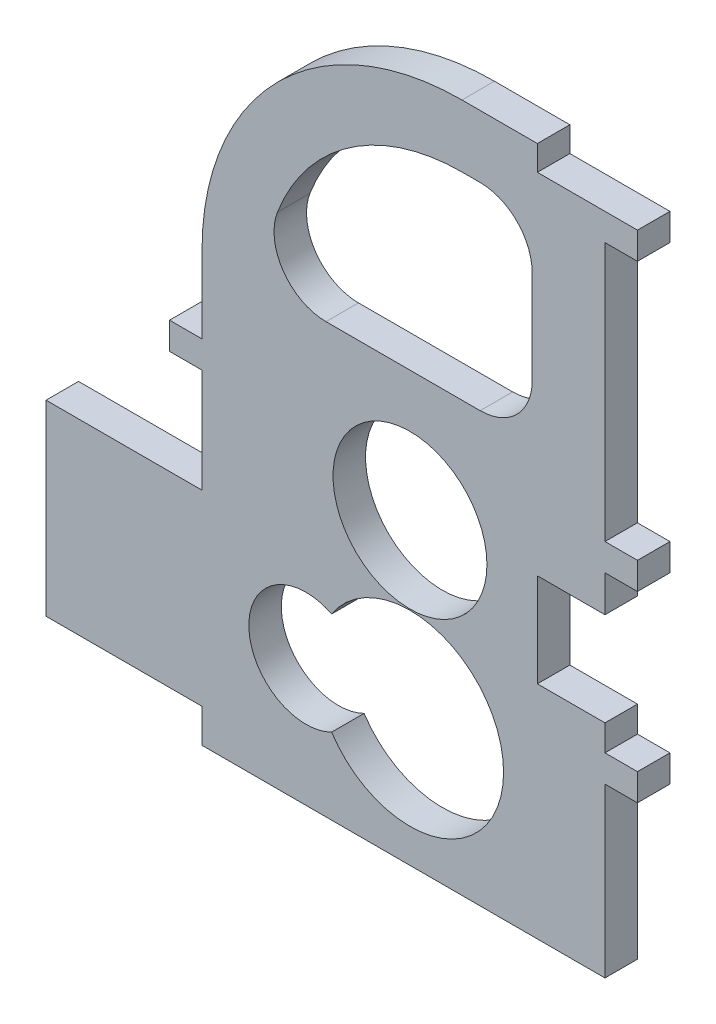
SolidWorks part; units mm, degrees
material "Balsa"
ref_plane "Front Plane" through (0, 0, 0) normal (0, 0, 1) x (1, 0, 0)
ref_plane "Top Plane" through (0, 0, 0) normal (0, 1, 0) x (1, 0, 0)
ref_plane "Right Plane" through (0, 0, 0) normal (1, 0, 0) x (0, 0, -1)
sketch "Sketch1" plane through (0, 0, 0) normal (0, 0, 1) x (1, 0, 0)
  line L0 (0, -1000) -> (0, 49000) construction
  line L1 (-1000, 0) -> (49000, 0) construction
  line L2 (0, -8.382) -> (-5.08, -8.382)
  line L3 (9.525, 16.51) -> (11.1125, 16.51)
  line L4 (2.54, 19.05) -> (9.525, 19.05)
  line L5 (9.525, -14.605) -> (-10.16, -14.605)
  line L6 (-10.16, -14.605) -> (-10.16, 6.35)
  line L7 (9.525, 19.05) -> (9.525, -14.605)
  line L8 (-11.7475, 1.27) -> (-10.16, 1.27)
  line L9 (-11.7475, 1.27) -> (-11.7475, 2.5908)
  line L10 (-11.7475, 2.5908) -> (-10.16, 2.5908)
  line L11 (-10.16, 1.27) -> (-10.16, 2.5908)
  line L12 (9.525, 2.54) -> (11.1125, 2.54)
  line L13 (9.525, 2.54) -> (9.525, 3.8608)
  line L14 (9.525, 3.8608) -> (11.1125, 3.8608)
  line L15 (11.1125, 2.54) -> (11.1125, 3.8608)
  line L16 (9.525, 16.51) -> (9.525, 17.8308)
  line L17 (9.525, 17.8308) -> (11.1125, 17.8308)
  line L18 (11.1125, 16.51) -> (11.1125, 17.8308)
  line L19 (-7.112, 6.35) -> (5.969, 6.35)
  line L20 (-10.16, -12.954) -> (-17.78, -12.954)
  line L21 (5.969, 6.35) -> (5.969, 16.002)
  line L22 (-10.16, -3.81) -> (-17.78, -3.81)
  line L23 (-17.78, -12.954) -> (-17.78, -3.81)
  line L24 (5.969, 16.002) -> (2.54, 16.002)
  line L27 (9.525, -6.4008) -> (11.1125, -6.4008)
  line L28 (9.525, -6.4008) -> (9.525, -5.08)
  line L29 (9.525, -5.08) -> (11.1125, -5.08)
  line L30 (11.1125, -6.4008) -> (11.1125, -5.08)
  circle A0 centre (0, 0) radius 3.7592
  arc A1 (-3.829, -10.8803) -> (-3.829, -5.8837) centre (0, -8.382) ccw
  arc A2 (-3.829, -5.8837) -> (-3.829, -10.8803) centre (-5.08, -8.382) ccw
  arc A3 (2.54, 19.05) -> (-10.16, 6.35) centre (2.54, 6.35) ccw
  arc A4 (2.54, 16.002) -> (-7.112, 6.35) centre (2.54, 6.35) ccw
  arc A5 (2.54, 19.05) -> (-10.16, 6.35) centre (2.54, 6.35) ccw construction
  dimension "D1" = 7.5184
  dimension "D4" = 9.144
  dimension "D3" = 19.685
  dimension "D5" = 8.382
  dimension "D9" = 12.7
  dimension "D10" = 1.5875
  dimension "D16" = 3.81
  dimension "D7" = 5.588
  dimension "D6" = 5.08
  dimension "D8" = 9.525
  dimension "D11" = 9.144
  dimension "D12" = 1.3208
  dimension "D13" = 1.3208
  dimension "D14" = 1.5875
  dimension "D15" = 2
  dimension "D17" = 14.605
  dimension "D18" = 19.05
  dimension "D19" = 16.51
  dimension "D20" = 3.048
  dimension "D21" = 3.556
  dimension "D22" = 1.3208
  dimension "D23" = 1.5875
  dimension "D24" = 5.08
  dimension "D25" = 1.27
  dimension "D26" = 7.62
  dimension "D27" = 2.54
extrude "Boss-Extrude1" add sketch "Sketch1" along normal blind 1.5875 contours L4 A3 L7 A0 | L10 L9 L8 | L3 L18 L17 L7 | L12 L15 L14 L7 | A3 | L27 L30 L29 L7 | L23 L20 L6 L22 region at (10.3187, 17.1704, 0) region at (9.1351, 10.1854, 0) region at (10.3187, 3.2004, 0) region at (10.3187, -5.7404, 0) region at (-10.9538, 1.9304, 0) region at (-13.97, -8.382, 0)
sketch "Sketch2" plane through (0, 0, 1.5875) normal (0, 0, 1) x (1, 0, 0)
  line L1 (6.223, -3.81) -> (9.525, -3.81)
  line L2 (6.223, -3.81) -> (6.223, 0.762)
  line L3 (6.223, 0.762) -> (9.525, 0.762)
  line L4 (9.525, -3.81) -> (9.525, 0.762)
  line L5 (9.525, 2.54) -> (9.525, -5.08) construction
  line L7 (9.525, 19.05) -> (9.525, 17.8308) construction
  line L9 (6.223, 17.8308) -> (9.525, 17.8308)
  line L10 (6.223, 17.8308) -> (6.223, 21.59)
  line L11 (6.223, 21.59) -> (9.525, 21.59)
  line L12 (9.525, 17.8308) -> (9.525, 21.59)
  line L13 (9.525, 17.8308) -> (11.1125, 17.8308) construction
  point P9 (9.525, -1.524)
  point P10 (9.525, 19.7104)
  point P15 (9.525, 19.7104)
  line M4 (9.525, 19.05) -> (2.54, 19.05)
  line M12 (9.525, -5.08) -> (9.525, 2.54)
  line M20 (9.525, 17.8308) -> (9.525, 19.05)
  dimension "D1" = 4.572
  dimension "D2" = 3.302
  dimension "D3" = 3.7592
  dimension "D4" = 3.302
  dimension "D5" = 0.762
extrude "Cut-Extrude1" cut sketch "Sketch2" against normal up to next contours L3 L2 L4 M12 | L10 L9 M20 M4 region at (7.874, -1.524, 1.5875) region at (7.874, 18.4404, 1.5875)
fillet "Fillet1" radius 2.54 3 edges at (-7.112, 6.35, 0.7937) (5.969, 16.002, 0.7937) (5.969, 6.35, 0.7937)
